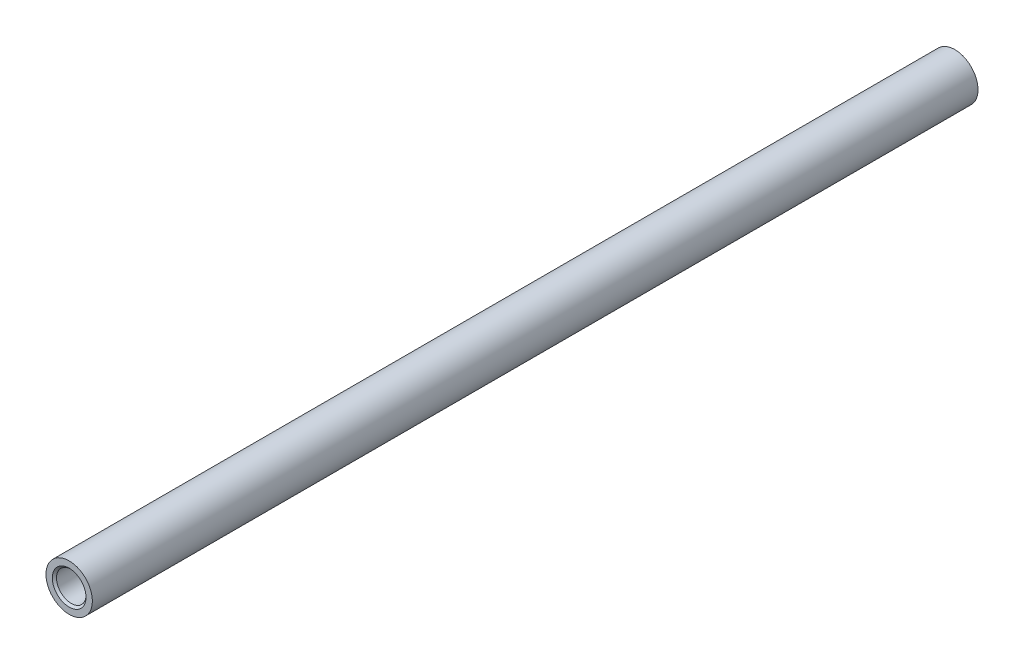
SolidWorks part; units mm, degrees
material "1.0545 (S355N)"
ref_plane "Płaszczyzna przednia" through (0, 0, 0) normal (0, 0, 1) x (1, 0, 0)
ref_plane "Płaszczyzna górna" through (0, 0, 0) normal (0, 1, 0) x (1, 0, 0)
ref_plane "Płaszczyzna prawa" through (0, 0, 0) normal (1, 0, 0) x (0, 0, -1)
sketch "Szkic1" plane through (0, 0, 0) normal (0, 0, 1) x (1, 0, 0)
  circle A0 centre (0, 0) radius 11
  circle A1 centre (0, 0) radius 7
  dimension "D1" = 22
  dimension "D2" = 4
extrude "Dodanie-wyciągnięcie1" add sketch "Szkic1" along normal mid plane 420
sketch "Szkic2" plane through (0, 0, -210) normal (0, 0, -1) x (-1, 0, 0)
  circle A0 centre (0, 0) radius 8
  circle A1 centre (0, 0) radius 7 construction
  dimension "D1" = 1
extrude "Wytnij-wyciągnięcie1" cut sketch "Szkic2" against normal blind 50
chamfer "Sfazowanie1" distance 1 angle 45 1 edges at (7, 0, 210)
